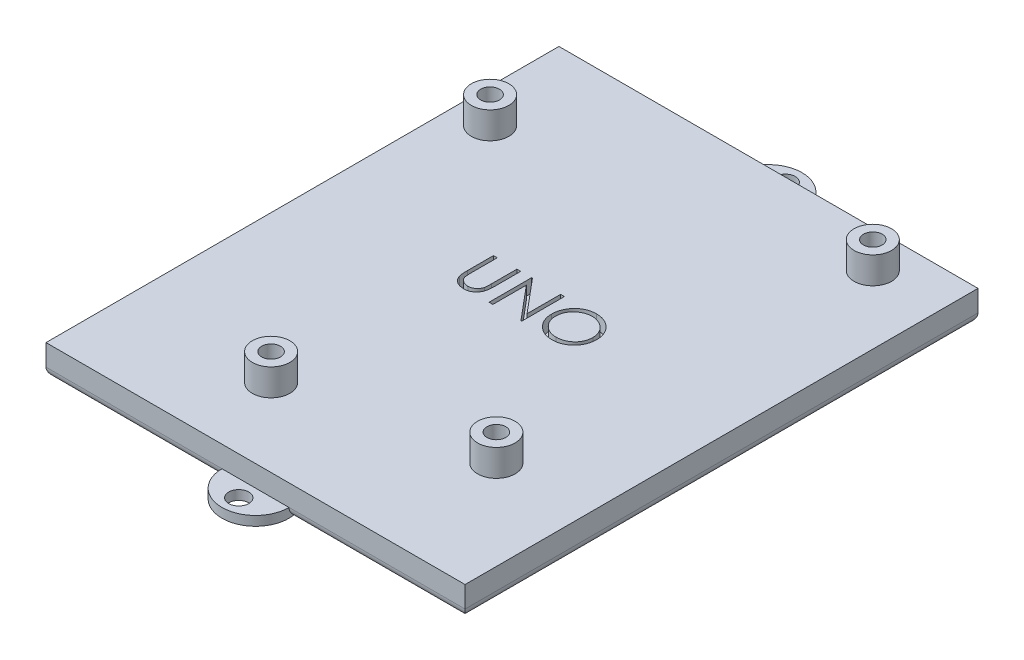
SolidWorks part; units mm, degrees
ref_plane "Front Plane" through (0, 0, 0) normal (0, 0, 1) x (1, 0, 0)
ref_plane "Top Plane" through (0, 0, 0) normal (0, 1, 0) x (1, 0, 0)
ref_plane "Right Plane" through (0, 0, 0) normal (1, 0, 0) x (0, 0, -1)
sketch "Sketch1" plane through (0, 0, 0) normal (0, 1, 0) x (1, 0, 0)
  line L0 (-31.25, 38.25) -> (31.25, 38.25)
  line L5 (-31.25, 38.25) -> (-31.25, -38.25)
  line L6 (-31.25, -38.25) -> (31.25, -38.25)
  line L7 (31.25, 38.25) -> (31.25, -38.25)
  point P11 (-31.25, 0)
  point P12 (0, -38.25)
  dimension "D3" = 76.5
  dimension "D4" = 62.5
extrude "Boss-Extrude1" add sketch "Sketch1" along normal blind 4.575
sketch "Sketch2" plane through (0, 4.575, 0) normal (0, 1, 0) x (1, 0, 0)
  line L0 (17.8977, -20.2309) -> (6.2677, 29.2199) construction
  line L1 (21.1029, 32.709) -> (6.2677, 29.2199) construction
  line L2 (17.8977, -20.2309) -> (-9.3002, -26.6274) construction
  line L3 (-9.3002, -26.6274) -> (-21.221, 24.0597) construction
  line L4 (0, -38.25) -> (0, 38.25) construction
  line L5 (-31.25, 0) -> (31.25, 0) construction
  line L6 (-21.221, 24.0597) -> (-26.1661, 22.8967) construction
  line L11 (-31.25, 38.25) -> (-31.25, -38.25) construction
  line L12 (-31.25, -38.25) -> (31.25, -38.25) construction
  line L13 (31.25, 38.25) -> (-31.25, 38.25) construction
  line L14 (31.25, -38.25) -> (31.25, 38.25) construction
  circle A0 centre (17.8977, -20.2309) radius 2.8
  circle A1 centre (21.1029, 32.709) radius 2.8
  circle A2 centre (-26.1661, 22.8967) radius 2.8
  circle A3 centre (-9.3002, -26.6274) radius 2.8
  circle A4 centre (21.1029, 32.709) radius 1.4
  circle A5 centre (17.8977, -20.2309) radius 1.4
  circle A6 centre (-9.3002, -26.6274) radius 1.4
  circle A7 centre (-26.1661, 22.8967) radius 1.4
  dimension "D7" = 2.8
  dimension "D10" = 1.4
  dimension "D1" = 27.94
  dimension "D2" = 15.24
  dimension "D3" = 5.08
  dimension "D4" = 1.27
  dimension "D5" = 50.8
  dimension "D6" = 13.235
  dimension "D8" = 9.3002
  dimension "D9" = 26.6274
extrude "Boss-Extrude2" add sketch "Sketch2" along normal blind 4
sketch "Sketch3" plane through (0, 4.575, 0) normal (0, 1, 0) x (1, 0, 0)
  circle A0 centre (17.8977, -20.2309) radius 1.4
  circle A1 centre (-9.3002, -26.6274) radius 1.4
  circle A2 centre (-26.1661, 22.8967) radius 1.4
  circle A3 centre (21.1029, 32.709) radius 1.4
  circle A4 centre (21.1029, 32.709) radius 1.4 construction
  circle A5 centre (-26.1661, 22.8967) radius 1.4 construction
extrude "Cut-Extrude1" cut sketch "Sketch3" against normal offset from surface (3.575 mm away) 1 up to face at (0, 0, 0)
sketch "Sketch4" plane through (0, 0, 0) normal (0, 1, 0) x (1, 0, 0)
  line L0 (-5, -38.25) -> (5, -38.25)
  line L2 (-31.25, -38.25) -> (31.25, -38.25) construction
  line L4 (0, -38.25) -> (0, -43.25) construction
  arc A0 (-5, -38.25) -> (5, -38.25) centre (0, -38.25) ccw
  circle A2 centre (0, -40.75) radius 1.5
  dimension "D2" = 3
  dimension "D3" = 5
extrude "Boss-Extrude3" add sketch "Sketch4" along normal blind 1.4
mirror "Mirror1" about plane through (0, 0, 0) normal (0, 0, 1) of "Boss-Extrude3"
sketch "Sketch5" plane through (0, 4.575, 0) normal (0, 1, 0) x (1, 0, 0)
  line L0 (-15, 0) -> (15, 0) construction
  text T0 "UNO" font "Century Gothic" height in points 24
  point P4 (14.3725, 0)
  point P5 (10.1548, 0)
  point P6 (0, 0)
  point P7 (0, 0)
  dimension "D1" = 30
extrude "Cut-Extrude2" cut sketch "Sketch5" against normal blind 2
fillet "Fillet1" radius 1.4 6 edges at (-18.125, 0, 38.25) (18.125, 0, 38.25) (31.25, 0, 0) (18.125, 0, -38.25) (-18.125, 0, -38.25) (-31.25, 0, 0)
